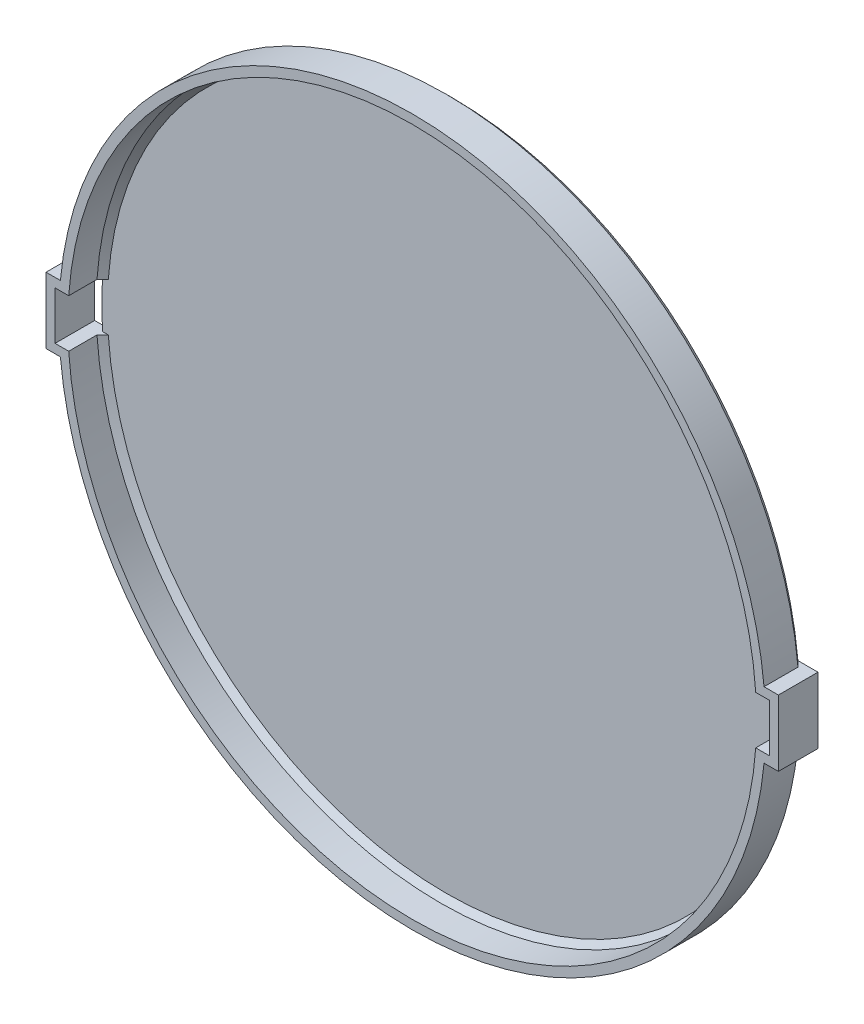
SolidWorks part; units mm, degrees
ref_plane "Front" through (0, 0, 0) normal (0, 0, 1) x (1, 0, 0)
ref_plane "Top" through (0, 0, 0) normal (0, 1, 0) x (1, 0, 0)
ref_plane "Right" through (0, 0, 0) normal (1, 0, 0) x (0, 0, -1)
sketch "Sketch1" plane through (0, 0, 0) normal (0, 0, 1) x (1, 0, 0)
  line L0 (-60.65, 4.25) -> (-60.65, -4.25)
  line L1 (-60.65, 4.25) -> (-63.1627, 4.25)
  line L2 (-63.1627, 4.25) -> (-63.1627, -4.25)
  line L3 (-63.1627, -4.25) -> (-60.65, -4.25)
  line L4 (-62.2256, 5.85) -> (-64.7627, 5.85)
  line L5 (-64.7627, 5.85) -> (-64.7627, -5.85)
  line L6 (-62.2256, -5.85) -> (-64.7627, -5.85)
  circle A0 centre (0, 0) radius 62.5
  circle A1 centre (0, 0) radius 60.9
  point P8 (-60.65, 0)
  dimension "D1" = 125
  dimension "D2" = 1.6
  dimension "D3" = 8.5
  dimension "D4" = 60.65
  dimension "D5" = 2.5127
  dimension "D6" = 1.6
  dimension "D7" = 1.6
  dimension "D8" = 1.6
extrude "Boss-Extrude1" add sketch "Sketch1" along normal blind 6 contours A1 L3 A0 L1 | A1 L1 A0 L3 region at (-61.6511, 0, 0) region at (-61.5534, 6.0167, 0)
extrude "Boss-Extrude2" add sketch "Sketch1<2>" against normal blind 1 contours A0
sketch "Sketch1<2>" plane through (0, 0, 0) normal (0, 0, 1) x (1, 0, 0) same geometry as "Sketch1"
extrude "Cut-Extrude1" cut sketch "Sketch1<4>" along normal through all and the other way through all contours A1 L1 A0 L3 region at (-61.6511, 0, 0)
sketch "Sketch1<4>" plane through (0, 0, 0) normal (0, 0, 1) x (1, 0, 0) same geometry as "Sketch1"
extrude "Boss-Extrude3" add sketch "Sketch1<5>" along normal up to surface (6 mm away) and the other way up to surface (1 mm away) contours A0 L4 L5 L6 L3 L2 L1 region at (-63.803, 0, 0) up to face at (0.0733, 0, 6) other way up to face at (-30.3767, 0, -1)
sketch "Sketch1<5>" plane through (0, 0, 0) normal (0, 0, 1) x (1, 0, 0) same geometry as "Sketch1"
mirror "Mirror1" about plane through (0, 0, 0) normal (1, 0, 0) of "Boss-Extrude3", "Cut-Extrude1"
chamfer "Chamfer1" distance 1 angle 45 4 edges at (0, -60.9, 0) (0, 60.9, 0) (0, 62.5, -1) (0, -62.5, -1)
